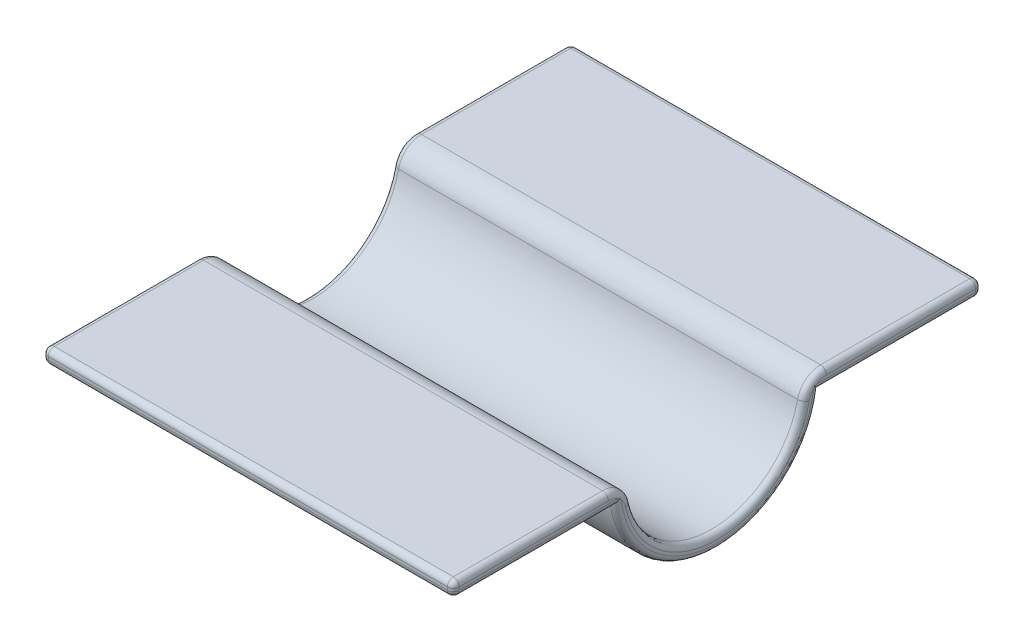
SolidWorks part; units mm, degrees
ref_plane "Front Plane" through (0, 0, 0) normal (0, 0, 1) x (1, 0, 0)
ref_plane "Top Plane" through (0, 0, 0) normal (0, 1, 0) x (1, 0, 0)
ref_plane "Right Plane" through (0, 0, 0) normal (1, 0, 0) x (0, 0, -1)
sketch "Sketch1" plane through (0, 0, 0) normal (1, 0, 0) x (0, 0, -1)
  line L0 (-45, 0) -> (-15, 0)
  line L1 (45, 0) -> (45, -2.5)
  line L2 (45, -2.5) -> (17.3205, -2.5)
  line L3 (-45, -2.5) -> (-45, 0)
  line L4 (15, 0) -> (45, 0)
  line L5 (-17.3205, -2.5) -> (-45, -2.5)
  arc A0 (-15, 0) -> (15, 0) centre (0, 0) ccw
  arc A1 (-17.3205, -2.5) -> (17.3205, -2.5) centre (0, 0) ccw
  point P7 (0, 0)
  dimension "D1" = 30
  dimension "D2" = 2.5
  dimension "D3" = 2.5
  dimension "D4" = 30
extrude "Boss-Extrude1" add sketch "Sketch1" along normal blind 70
fillet "Fillet1" radius 1 4 edges at (35, -2.5, -45) (35, 0, -45) (35, -2.5, 45) (35, 0, 45)
fillet "Fillet2" radius 4 2 edges at (35, 0, -15) (35, 0, 15)
fillet "Fillet3" radius 1 28 edges at (0, -0.8881, 16.0611) (0, 0, 31.2871) (0, -0.2929, 44.7071) (0, -1.25, 45) (0, -2.2071, 44.7071) (0, -2.5, 30.6603) (0, -17.5, 0) (0, -2.5, -30.6603) (0, -2.2071, -44.7071) (0, -1.25, -45) (0, -0.2929, -44.7071) (0, 0, -31.2871) (0, -0.8881, -16.0611) (0, -15, 0) (70, -0.2929, -44.7071) (70, -1.25, -45) (70, -2.2071, -44.7071) (70, -2.5, -30.6603) (70, -17.5, 0) (70, -2.5, 30.6603) (70, -2.2071, 44.7071) (70, -1.25, 45) (70, -0.2929, 44.7071) (70, 0, 31.2871) (70, -0.8881, 16.0611) (70, -15, 0) (70, -0.8881, -16.0611) (70, 0, -31.2871)
